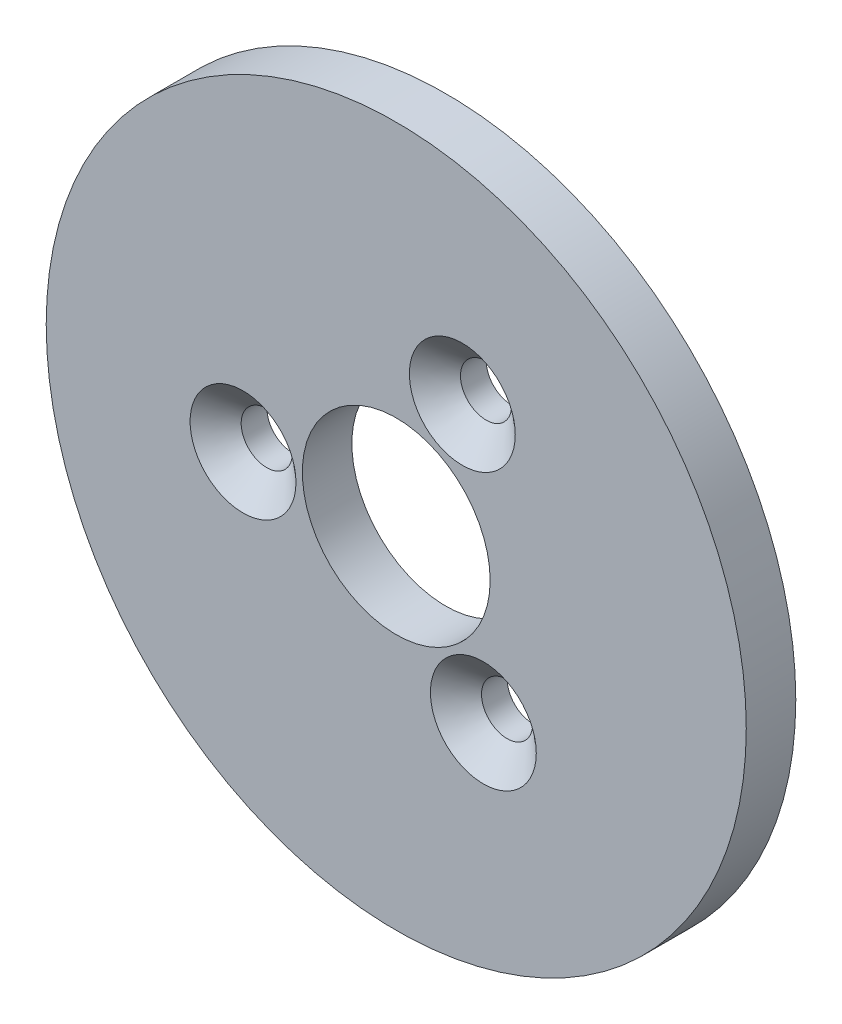
SolidWorks part; units mm, degrees
material "Acrylic (Medium-high impact)"
ref_plane "Front Plane" through (0, 0, 0) normal (0, 0, 1) x (1, 0, 0)
ref_plane "Top Plane" through (0, 0, 0) normal (0, 1, 0) x (1, 0, 0)
ref_plane "Right Plane" through (0, 0, 0) normal (1, 0, 0) x (0, 0, -1)
sketch "Sketch1" plane through (0, 0, 0) normal (0, 0, 1) x (1, 0, 0)
  circle A0 centre (0, 0) radius 20.5
  dimension "D1" = 41
extrude "Boss-Extrude1" add sketch "Sketch1" along normal blind 2.9
sketch "Sketch2" plane through (0, 0, 2.9) normal (0, 0, 1) x (1, 0, 0)
  circle A3 centre (-8.9719, -0.7111) radius 1.5
  circle A4 centre (-8.9719, -0.7111) radius 1.5
  circle A5 centre (5.1018, -7.4143) radius 1.5
  circle A6 centre (5.1018, -7.4143) radius 1.5
  circle A7 centre (3.8701, 8.1254) radius 1.5
  circle A8 centre (3.8701, 8.1254) radius 1.5
  dimension "D2" = 0
  dimension "D3" = 0
  dimension "D4" = 0
extrude "Cut-Extrude1" cut sketch "Sketch2" against normal through all
chamfer "Chamfer1" distance 1.6 angle 41 3 edges at (-7.4719, -0.7111, 2.9) (5.3701, 8.1254, 2.9) (6.6018, -7.4143, 2.9) first distance on face at (6.6018, -7.4143, 2.9)
sketch "Sketch3" plane through (0, 0, 2.9) normal (0, 0, 1) x (1, 0, 0)
  circle A1 centre (0, 0) radius 5.5
  circle A2 centre (0, 0) radius 5.5
  dimension "D1" = 0
extrude "Cut-Extrude2" cut sketch "Sketch3" against normal through all
equation "\"smallPulleyTeeth\"= 15"
equation "\"largePulleyTeeth\"= 30"
equation "\"eighthThick\"= 2.9mm"
equation "\"sixteenthThick\" = 1.7mm"
equation "\"quarterThick\"=6.0mm"
equation "\"OD\" = 145mm"
equation "\"puckAngle\" = 60.5deg"
equation "\"puckDiam\" = 76.5mm"
equation "\"axlePress\" = 5.9mm"
equation "\"press\" = 0.2mm"
equation "\"wheelClear\" = 0.3mm"
equation "\"10-32clear\" = 4.8mm"
equation "\"D1@Boss-Extrude1\"=\"eighthThick\""
equation "\"D1@Chamfer1\"=(6.5-\"6-32clear\")/2"
equation "\"6-32clear\" = 3.3mm"
equation "\"8-32clear\" = 4.0mm"
